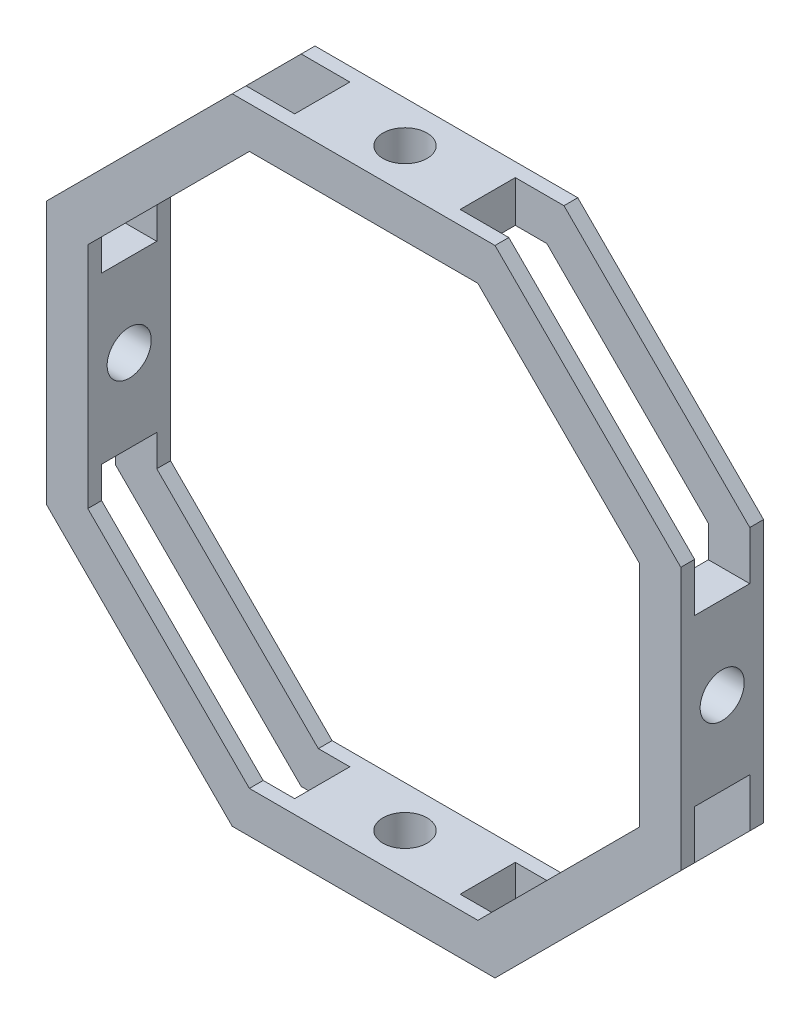
SolidWorks part; units mm, degrees
ref_plane "Plano frontal" through (0, 0, 0) normal (0, 0, 1) x (1, 0, 0)
ref_plane "Plano superior" through (0, 0, 0) normal (0, 1, 0) x (1, 0, 0)
ref_plane "Plano direito" through (0, 0, 0) normal (1, 0, 0) x (0, 0, -1)
sketch "Esboço1" plane through (0, 0, 0) normal (0, 0, 1) x (1, 0, 0)
  line L1 (115, 47.6346) -> (47.6346, 115)
  line L2 (47.6346, 115) -> (-47.6346, 115)
  line L3 (-47.6346, 115) -> (-115, 47.6346)
  line L4 (-115, 47.6346) -> (-115, -47.6346)
  line L5 (-115, -47.6346) -> (-47.6346, -115)
  line L6 (-47.6346, -115) -> (47.6346, -115)
  line L7 (47.6346, -115) -> (115, -47.6346)
  line L8 (115, -47.6346) -> (115, 47.6346)
  line L9 (100, 41.4214) -> (41.4214, 100)
  line L10 (41.4214, 100) -> (-41.4214, 100)
  line L11 (-41.4214, 100) -> (-100, 41.4214)
  line L12 (-100, 41.4214) -> (-100, -41.4214)
  line L13 (-100, -41.4214) -> (-41.4214, -100)
  line L14 (-41.4214, -100) -> (41.4214, -100)
  line L15 (41.4214, -100) -> (100, -41.4214)
  line L16 (100, -41.4214) -> (100, 41.4214)
  circle A0 centre (0, 0) radius 115 construction
  circle A1 centre (0, 0) radius 100 construction
extrude "Ressalto-extrusão1" add sketch "Esboço1" along normal blind 30
sketch "Esboço2" plane through (115, 0, 0) normal (1, 0, 0) x (0, 0, -1)
  line L0 (-30, -47.6346) -> (-30, 47.6346) construction
  line L1 (0, 0) -> (-30, 0)
  line L2 (0, 0) -> (0, 30)
  line L3 (0, 30) -> (-30, 30)
  line L4 (-30, 0) -> (-30, 30)
  line L5 (-30, -47.6346) -> (0, -47.6346) construction
  line L6 (0, 0) -> (-30, 0)
  line L7 (0, 0) -> (0, -30)
  line L8 (0, -30) -> (-30, -30)
  line L9 (-30, 0) -> (-30, -30)
  line L10 (0, 47.6346) -> (-5, 47.6346)
  line L11 (0, 47.6346) -> (0, 30)
  line L12 (0, 30) -> (-5, 30)
  line L13 (-5, 47.6346) -> (-5, 30)
  line L14 (-30, 47.6346) -> (-25, 47.6346)
  line L15 (-30, 47.6346) -> (-30, 30)
  line L16 (-30, 30) -> (-25, 30)
  line L17 (-25, 47.6346) -> (-25, 30)
  line L18 (-5, -30) -> (-25, -30)
  line L19 (-5, -30) -> (-5, -47.6346)
  line L20 (-5, -47.6346) -> (-25, -47.6346)
  line L21 (-25, -30) -> (-25, -47.6346)
  circle A0 centre (-15, 0) radius 8
  line M2 (0, 47.6346) -> (-30, 47.6346)
  line M4 (-30, -47.6346) -> (0, -47.6346)
extrude "Corte-extrusão1" cut sketch "Esboço2" against normal through all both and the other way through all contours L17 L3 L13 M2 | L8 L21 L19 M4 | L6 A0 | L6 A0 region at (115, -3.3953, 15) region at (115, 3.3953, 15) region at (115, 38.8173, 15) region at (115, -38.8173, 15)
sketch "Esboço3" plane through (0, 115, 0) normal (0, 1, 0) x (1, 0, 0)
  line L0 (47.6346, -30) -> (-47.6346, -30) construction
  line L1 (0, 0) -> (30, 0)
  line L2 (0, 0) -> (0, -30)
  line L3 (0, -30) -> (30, -30)
  line L4 (30, 0) -> (30, -30)
  line L5 (47.6346, -30) -> (47.6346, 0) construction
  line L6 (0, 0) -> (-30, 0)
  line L7 (0, 0) -> (0, -30)
  line L8 (0, -30) -> (-30, -30)
  line L9 (-30, 0) -> (-30, -30)
  line L10 (-47.6346, 0) -> (-30, 0)
  line L11 (-47.6346, 0) -> (-47.6346, -5)
  line L12 (-47.6346, -5) -> (-30, -5)
  line L13 (-30, 0) -> (-30, -5)
  line L14 (-47.6346, -30) -> (-30, -30)
  line L15 (-47.6346, -30) -> (-47.6346, -25)
  line L16 (-47.6346, -25) -> (-30, -25)
  line L17 (-30, -30) -> (-30, -25)
  line L18 (30, -25) -> (47.6346, -25)
  line L19 (30, -25) -> (30, -5)
  line L20 (30, -5) -> (47.6346, -5)
  line L21 (47.6346, -25) -> (47.6346, -5)
  circle A0 centre (0, -15) radius 8
  line M2 (-47.6346, 0) -> (-47.6346, -30)
  line M4 (47.6346, -30) -> (47.6346, 0)
extrude "Corte-extrusão2" cut sketch "Esboço3" against normal through all both and the other way through all contours L7 A0 | L7 A0 | L20 L4 L18 M4 | L16 L9 L12 M2 region at (3.3953, 115, 15) region at (-3.3953, 115, 15) region at (38.8173, 115, 15) region at (-38.8173, 115, 15)
sketch "Esboço4" plane through (81.3173, 81.3173, 0) normal (0.7071, 0.7071, 0) x (0, 0, -1)
  line L0 (-25, -47.6346) -> (-5, -47.6346) construction
  line L1 (-25, 47.6346) -> (-5, 47.6346)
  line L2 (-25, 47.6346) -> (-25, -47.6346)
  line L3 (-25, -47.6346) -> (-5, -47.6346)
  line L4 (-5, 47.6346) -> (-5, -47.6346)
extrude "Corte-extrusão3" cut sketch "Esboço4" against normal through all both and the other way through all
sketch "Esboço5" plane through (-81.3173, 81.3173, 0) normal (-0.7071, 0.7071, 0) x (0, 0, 1)
  line L1 (25, 47.6346) -> (5, 47.6346)
  line L2 (25, 47.6346) -> (25, -47.6346)
  line L3 (25, -47.6346) -> (5, -47.6346)
  line L4 (5, 47.6346) -> (5, -47.6346)
extrude "Corte-extrusão4" cut sketch "Esboço5" against normal through all both and the other way through all
